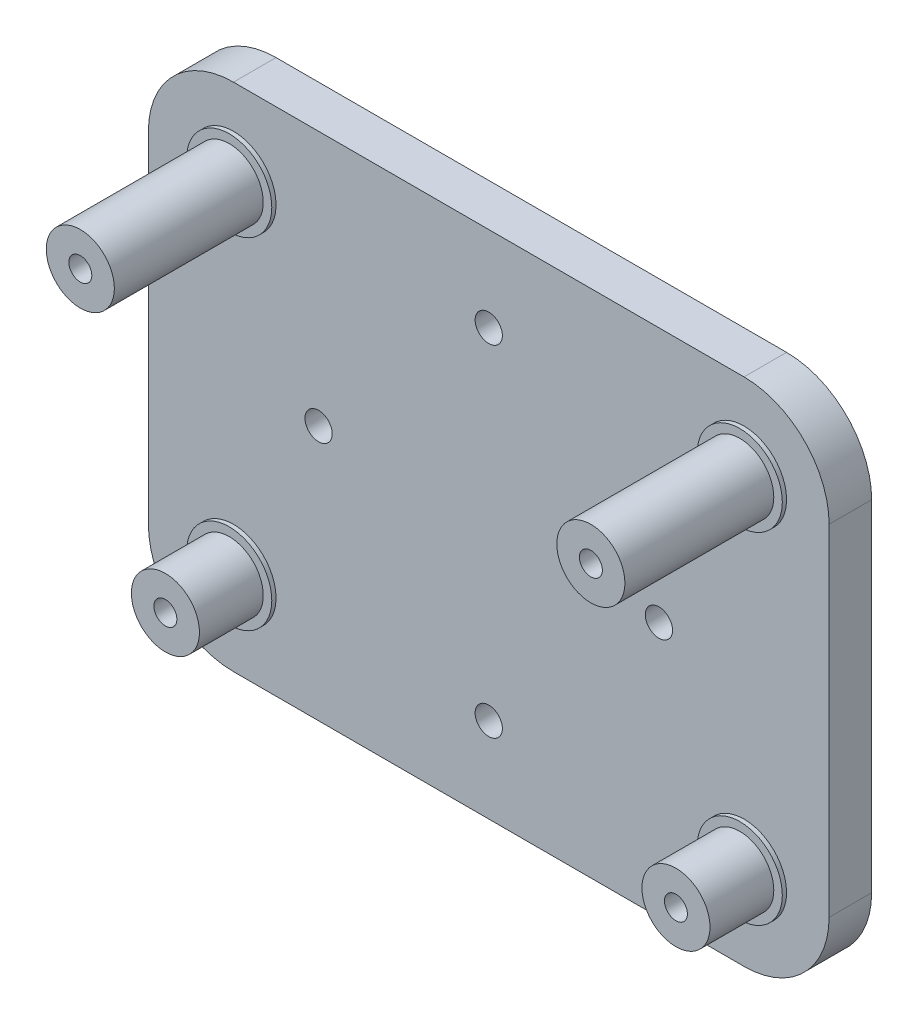
SolidWorks part; units mm, degrees
ref_plane "Front Plane" through (0, 0, 0) normal (0, 0, 1) x (1, 0, 0)
ref_plane "Top Plane" through (0, 0, 0) normal (0, 1, 0) x (1, 0, 0)
ref_plane "Right Plane" through (0, 0, 0) normal (1, 0, 0) x (0, 0, -1)
ref_axis "X" through (-88.99, 0, 0) along (1, 0, 0)
ref_axis "Y" through (0, 55, 0) along (0, -1, 0)
ref_axis "Z" through (0, 0, -88.99) along (0, 0, 1)
sketch "Sketch1" plane through (0, 0, 0) normal (0, 0, 1) x (1, 0, 0)
  line L0 (-20, 0) -> (20, 0) construction
  line L1 (-30, 20) -> (30, 20) construction
  line L2 (-30, 20) -> (-30, -20) construction
  line L3 (-30, -20) -> (30, -20) construction
  line L4 (30, 20) -> (30, -20) construction
  line L5 (-30, 20) -> (30, -20) construction
  line L6 (-30, -20) -> (30, 20) construction
  line L7 (-40, 30) -> (40, 30)
  line L8 (-40, 30) -> (-40, -30)
  line L9 (-40, -30) -> (40, -30)
  line L10 (40, 30) -> (40, -30)
  line L11 (-40, 30) -> (40, -30) construction
  line L12 (-40, -30) -> (40, 30) construction
  circle A0 centre (-30, 20) radius 4
  circle A1 centre (-30, -20) radius 4
  circle A2 centre (30, -20) radius 4
  circle A3 centre (30, 20) radius 4
  circle A4 centre (-30, 20) radius 5
  circle A5 centre (30, 20) radius 5
  circle A6 centre (30, -20) radius 5
  circle A7 centre (-30, -20) radius 5
  circle A8 centre (-30, 20) radius 1.35
  circle A9 centre (-30, -20) radius 1.35
  circle A10 centre (30, 20) radius 1.35
  circle A11 centre (30, -20) radius 1.35
  circle A12 centre (-20, 0) radius 1.6
  circle A13 centre (0, 20) radius 1.6
  circle A14 centre (20, 0) radius 1.6
  circle A15 centre (0, -20) radius 1.6
  point P0 (0, 0)
  point P10 (0, 0)
  point P31 (0, 0)
  dimension "D1" = 40
  dimension "D3" = 8
  dimension "D6" = 1
  dimension "D7" = 2.7
  dimension "D8" = 3.2
  dimension "D2" = 60
  dimension "D4" = 10
  dimension "D5" = 10
  dimension "D9" = 40
extrude "Boss-Extrude1" add sketch "Sketch1" against normal blind 5 contours L8 L9 L10 L7
extrude "Boss-Extrude2" add sketch "Sketch1<3>" along normal blind 8 contours A1 A9 | A2 A11 region at (-33.8869, -20, 0) region at (26.1131, -20, 0)
sketch "Sketch1<3>" plane through (0, 0, 0) normal (0, 0, 1) x (1, 0, 0) same geometry as "Sketch1"
extrude "Boss-Extrude4" add sketch "Sketch1<5>" along normal blind 18 contours A0 A8 | A3 A10 region at (-33.8869, 20, 0) region at (26.1131, 20, 0)
sketch "Sketch1<5>" plane through (0, 0, 0) normal (0, 0, 1) x (1, 0, 0) same geometry as "Sketch1"
extrude "Boss-Extrude3" add sketch "Sketch1<4>" along normal blind 0.5 contours A4 A0 | A5 A3 | A6 A2 | A7 A1 region at (-34.8586, 20, 0) region at (25.1414, 20, 0) region at (25.1414, -20, 0) region at (-34.8586, -20, 0)
sketch "Sketch1<4>" plane through (0, 0, 0) normal (0, 0, 1) x (1, 0, 0) same geometry as "Sketch1"
extrude "Cut-Extrude1" cut sketch "Sketch1<6>" against normal through all both and the other way through all contours A13 | A12 | A15 | A14 region at (-20, 0, 0) region at (0, 20, 0) region at (20, 0, 0) region at (0, -20, 0)
sketch "Sketch1<6>" plane through (0, 0, 0) normal (0, 0, 1) x (1, 0, 0) same geometry as "Sketch1"
fillet "Fillet1" radius 10 4 edges at (40, 30, -2.5) (40, -30, -2.5) (-40, -30, -2.5) (-40, 30, -2.5)
